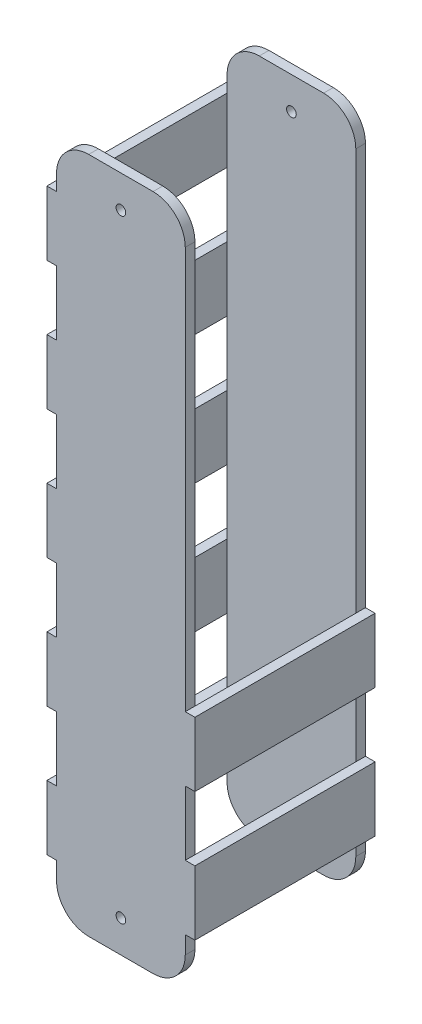
SolidWorks part; units mm, degrees
material "ENPH 253 Hardboard"
ref_plane "Front Plane" through (0, 0, 0) normal (0, 0, 1) x (1, 0, 0)
ref_plane "Top Plane" through (0, 0, 0) normal (0, 1, 0) x (1, 0, 0)
ref_plane "Right Plane" through (0, 0, 0) normal (1, 0, 0) x (0, 0, -1)
sketch "Sketch1" plane through (0, 0, 0) normal (0, 0, 1) x (1, 0, 0)
  line L1 (-10, 105.25) -> (10, 105.25)
  line L2 (-20, 95.25) -> (-20, -95.25)
  line L3 (-10, -105.25) -> (10, -105.25)
  line L4 (20, 95.25) -> (20, -95.25)
  line L5 (-20, 105.25) -> (20, -105.25) construction
  line L6 (-20, -105.25) -> (20, 105.25) construction
  arc A0 (10, -105.25) -> (20, -95.25) centre (10, -95.25) ccw
  arc A1 (-20, -95.25) -> (-10, -105.25) centre (-10, -95.25) ccw
  arc A2 (10, 105.25) -> (20, 95.25) centre (10, 95.25) cw
  arc A3 (-20, 95.25) -> (-10, 105.25) centre (-10, 95.25) cw
  point P0 (0, 0)
  dimension "D3" = 10
  dimension "D1" = 40
  dimension "D2" = 210.5
extrude "Boss-Extrude1" add sketch "Sketch1" along normal blind 3 from offset 50 contours L4 A0 L3 A1 L2 A3 L1 A2
extrude "Boss-Extrude2" add sketch "Sketch1<3>" against normal blind 3 separate body
sketch "Sketch1<3>" plane through (0, 0, 0) normal (0, 0, 1) x (1, 0, 0) same geometry as "Sketch1"
sketch "Sketch2" plane through (0, 0, 0) normal (0, 0, 1) x (1, 0, 0)
  line L0 (55, 0) -> (-55, 0) construction
  line L1 (-10, 105.25) -> (10, 105.25) construction
  circle A0 centre (0, 95.25) radius 1.5
  circle A1 centre (0, -95.25) radius 1.5
  dimension "D2" = 3
  dimension "D1" = 10
extrude "Cut-Extrude1" cut sketch "Sketch2" against normal through all both and the other way through all
sketch "Sketch3" plane through (-20, 0, 0) normal (-1, 0, 0) x (0, 0, 1)
  line L0 (-3, 95.25) -> (-3, -95.25) construction
  line L1 (-3, 90.25) -> (53, 90.25)
  line L2 (-3, 90.25) -> (-3, 70.25)
  line L3 (-3, 70.25) -> (53, 70.25)
  line L4 (53, 90.25) -> (53, 70.25)
  line L5 (53, 95.25) -> (53, -95.25) construction
  line L6 (53, 105.25) -> (50, 105.25) construction
  line L7 (-3, 50.25) -> (-3, 30.25)
  line L8 (-3, 50.25) -> (53, 50.25)
  line L9 (53, 50.25) -> (53, 30.25)
  line L10 (-3, 30.25) -> (53, 30.25)
  line L11 (-3, 10.25) -> (-3, -9.75)
  line L12 (-3, 10.25) -> (53, 10.25)
  line L13 (53, 10.25) -> (53, -9.75)
  line L14 (-3, -9.75) -> (53, -9.75)
  line L15 (-3, -29.75) -> (-3, -49.75)
  line L16 (-3, -29.75) -> (53, -29.75)
  line L17 (53, -29.75) -> (53, -49.75)
  line L18 (-3, -49.75) -> (53, -49.75)
  line L19 (-3, -69.75) -> (-3, -89.75)
  line L20 (-3, -69.75) -> (53, -69.75)
  line L21 (53, -69.75) -> (53, -89.75)
  line L22 (-3, -89.75) -> (53, -89.75)
  dimension "D1" = 20
  dimension "D2" = 15
  dimension "D3" = 5
extrude "Boss-Extrude4" add sketch "Sketch3" along normal blind 3
sketch "Sketch4" plane through (20, 0, 0) normal (1, 0, 0) x (0, 0, -1)
  line L0 (-53, -69.75) -> (-53, -89.75)
  line L1 (-53, -29.75) -> (3, -29.75)
  line L2 (-53, -29.75) -> (-53, -49.75)
  line L3 (-53, -49.75) -> (3, -49.75)
  line L4 (3, -29.75) -> (3, -49.75)
  line L5 (-53, -69.75) -> (3, -69.75)
  line L6 (3, -69.75) -> (3, -89.75)
  line L7 (-53, -89.75) -> (3, -89.75)
  dimension "D1" = 2
extrude "Boss-Extrude5" add sketch "Sketch4" along normal blind 3
